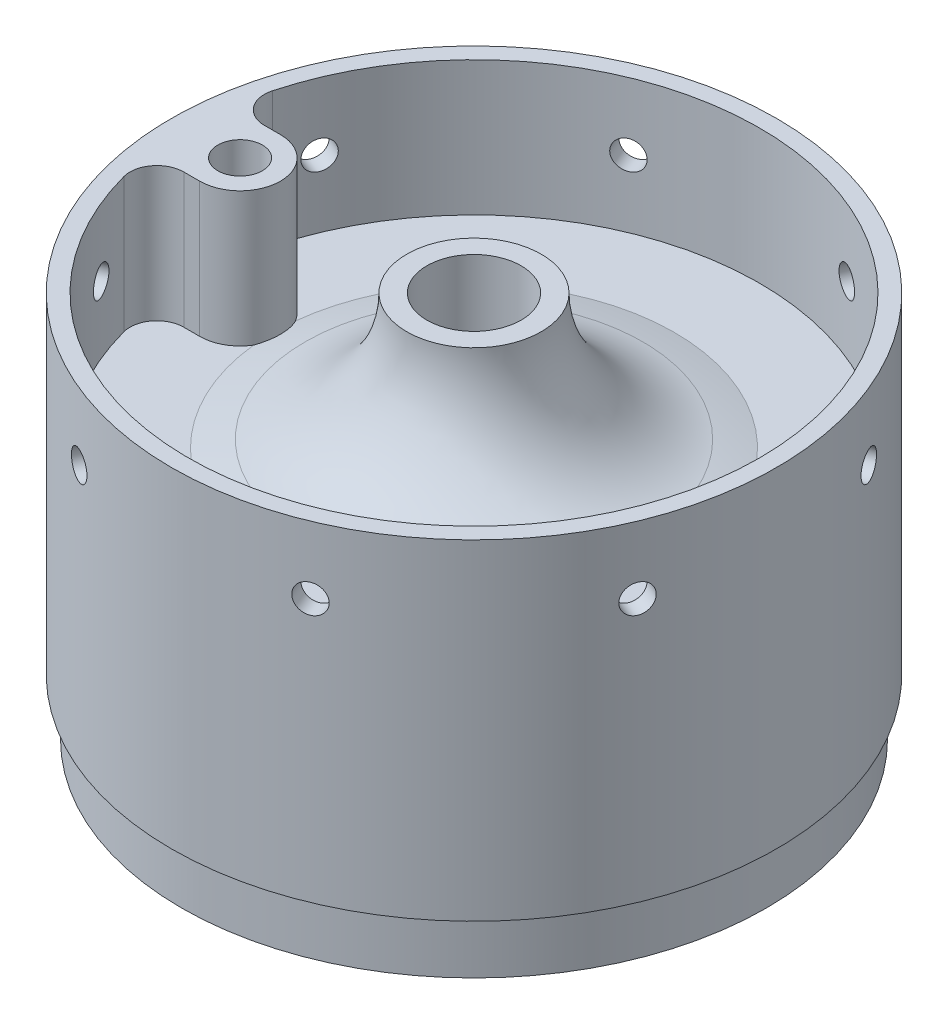
SolidWorks part; units mm, degrees
material "6061-T6 (SS)"
ref_plane "Front Plane" through (0, 0, 0) normal (0, 0, 1) x (1, 0, 0)
ref_plane "Top Plane" through (0, 0, 0) normal (0, 1, 0) x (1, 0, 0)
ref_plane "Right Plane" through (0, 0, 0) normal (1, 0, 0) x (0, 0, -1)
ref_axis "Axis1" through (0, 127.061, 0) along (0, -1, 0)
sketch "Sketch1" plane through (0, 0, 0) normal (0, 0, 1) x (1, 0, 0)
  line L0 (-57.15, 10.6249) -> (-57.15, 73.025)
  line L1 (-55.245, 9.525) -> (-57.15, 10.6249)
  line L2 (0, 127.061) -> (0, -81.9141) construction
  line L3 (-8.9065, 73.025) -> (-12.7, 73.025)
  line L4 (-55.245, 9.525) -> (-55.245, 0)
  line L5 (-55.245, 0) -> (-53.975, 0)
  line L6 (55, 0) -> (-55, 0) construction
  line L7 (-53.975, 73.025) -> (-57.15, 73.025)
  line L8 (-57.15, 10.6249) -> (-55.245, 9.525)
  line L9 (-53.975, 47.625) -> (-37.8832, 47.625)
  line L10 (-8.9065, 73.025) -> (-8.9065, 57.785)
  line L11 (-53.975, 47.625) -> (-53.975, 73.025)
  line L15 (-53.975, 0) -> (-53.975, 9.525)
  line L16 (-53.975, 9.525) -> (-51.7673, 22.0456)
  arc A0 (-51.7673, 22.0456) -> (-37.8832, 40.3817) centre (-32.7173, 22.0456) cw
  arc A1 (-37.8832, 40.3817) -> (-22.9779, 43.7136) centre (0, -94.0837) cw
  arc A2 (-31.8881, 49.0933) -> (-12.7, 73.025) centre (-37.2181, 73.025) ccw
  arc A3 (-37.8832, 47.625) -> (-31.8881, 49.0933) centre (0, -94.0837) cw
  arc A4 (-8.9065, 57.785) -> (-22.9779, 43.7136) centre (-22.9779, 57.785) cw
  point P14 (-54.61, 0)
  dimension "D5" = 19.05
  dimension "D6" = 139.7
  dimension "D7" = 146.685
  dimension "D8" = 63.5
  dimension "D14" = 15.24
  dimension "D2" = 170
  dimension "D3" = 9.525
  dimension "D4" = 1.27
  dimension "D9" = 25.4
  dimension "D10" = 3.175
  dimension "D11" = 12.7
  dimension "D13" = 8.9065
  dimension "D15" = 3.175
  dimension "D16" = 57.15
  dimension "D17" = 120
revolve "Revolve2" add sketch "Sketch1" angle 360 about axis through (0, 127.061, 0) along (0, -1, 0) region at (-38.0177, 44.7504, 0)
sketch "Sketch2" plane through (0, 0, 0) normal (0, 0, 1) x (1, 0, 0)
  line L0 (0, 127.061) -> (0, -81.9141) construction
  line L1 (0, 87.1374) -> (-97.8719, 87.1374)
  line L2 (0, 87.1374) -> (0, -26.2798)
  line L3 (0, -26.2798) -> (-97.8719, -26.2798)
  line L4 (-97.8719, 87.1374) -> (-97.8719, -26.2798)
revolve "Cut-Revolve1" [suppressed] cut sketch "Sketch2" angle 315 about axis through (0, 127.061, 0) along (0, -1, 0)
ref_plane "Plane1" through (0, 60.325, 0) normal (0, 1, 0) x (1, 0, 0)
ref_plane "Plane2" through (0, 0, 0) normal (0.9239, 0, 0.3827) x (0, -1, 0)
ref_axis "Axis2" through (83.9699, 60.325, -202.7212) along (-0.3827, 0, 0.9239)
hole_wizard "#3 (0.213) Diameter Hole1" positions "3DSketch3" profile "Sketch5" hole size "#3" standard "ANSI Inch"
sketch3d "3DSketch3"
  line L0 (83.9699, 60.325, -202.7212) -> (-38.5912, 60.325, 93.1674) construction
  point P0 (-21.8704, 60.325, 52.7997)
sketch "Sketch5" plane through (-21.8704, 60.325, 52.7997) normal (0, 1, 0) x (0.9239, 0, 0.3827)
  line L0 (0, 0) -> (0, 13.3094)
  line L1 (0, 13.3094) -> (2.7051, 11.684)
  line L2 (2.7051, 11.684) -> (2.7051, 0)
  line L5 (2.7051, 0) -> (0, 0)
  line L10 (0, 13.3094) -> (-2.7051, 11.684) construction
  line L11 (0, -6.35) -> (0, 107.95) construction
  dimension "Hole Dia." = 5.4102
  dimension "Hole Depth" = 11.684
  dimension "Drill Angle" = 118
pattern_circular "CirPattern1" count 8 over 360 about axis through (0, 127.061, 0) along (0, -1, 0) of "#3 (0.213) Diameter Hole1"
cosmetic thread "Cosmetic Thread1" parameters "D2"=6.35
hole_wizard "Q (0.332) Diameter Hole2" positions "Sketch9" profile "Sketch10" hole size "Q" standard "ANSI Inch" end condition through all
sketch "Sketch9" plane through (0, 47.625, 0) normal (0, 1, 0) x (1, 0, 0)
  line L0 (-40.1638, 0) -> (40.1638, 0) construction
  circle A1 centre (0, 0) radius 37.8832 construction
  point P0 (-44.196, 0)
  dimension "D1" = 44.196
sketch "Sketch10" plane through (-44.196, 47.625, 0) normal (1, 0, 0) x (0, 0, 1)
  line L0 (0, 0) -> (0, 47.625)
  line L1 (0, 47.625) -> (4.2164, 47.625)
  line L2 (4.2164, 47.625) -> (4.2164, 0)
  line L5 (4.2164, 0) -> (0, 0)
  line L11 (0, -6.35) -> (0, 107.95) construction
  dimension "Thru Hole Dia." = 8.4328
  dimension "Thru Hole Depth" = 47.625
sketch "Sketch11" plane through (0, 47.625, 0) normal (0, 1, 0) x (1, 0, 0)
  line L0 (-53.4344, 7.62) -> (-44.196, 7.62)
  line L1 (-53.4344, -7.6199) -> (-44.1961, -7.62)
  circle A0 centre (0, 0) radius 53.975 construction
  arc A2 (-44.196, 7.62) -> (-44.1961, -7.62) centre (-44.196, 0) cw
  circle A3 centre (-44.196, 0) radius 4.2164 construction
  circle A5 centre (0, 0) radius 53.975
  arc A6 (-53.4344, 7.62) -> (-53.4344, -7.6199) centre (0, 0) ccw
  point P4 (-41.2763, -6.8612)
  point P5 (-41.7852, -7.62)
  point P11 (0, 0)
  point P12 (0, 0)
  point P13 (-44.196, -7.6199)
  dimension "D1" = 7.62
  dimension "D2" = 7.62
  dimension "D3" = 180
  dimension "D4" = 0
extrude "Boss-Extrude1" add sketch "Sketch11" along normal up to surface (25.4 mm away) up to face at (0, 73.025, 57.15)
hole_wizard "Q (0.332) Diameter Hole3" positions "Sketch13" profile "Sketch12" hole size "Q" standard "ANSI Inch" end condition through all
sketch "Sketch13" plane through (0, 47.625, 0) normal (0, -1, 0) x (-1, 0, 0)
  circle A1 centre (44.196, 0) radius 4.2164 construction
  point P0 (44.196, 0)
  point P3 (0, 0)
  point P6 (0, 0)
sketch "Sketch12" plane through (-44.196, 47.625, 0) normal (1, 0, 0) x (0, 0, -1)
  line L0 (0, 0) -> (0, 25.4)
  line L1 (0, 25.4) -> (4.2164, 25.4)
  line L2 (4.2164, 25.4) -> (4.2164, 0)
  line L5 (4.2164, 0) -> (0, 0)
  line L11 (0, -6.35) -> (0, 107.95) construction
  dimension "Thru Hole Dia." = 8.4328
  dimension "Thru Hole Depth" = 25.4
fillet "Fillet1" radius 5.08 2 edges at (-53.4344, 60.325, -7.62) (-53.4344, 60.325, 7.6199)
